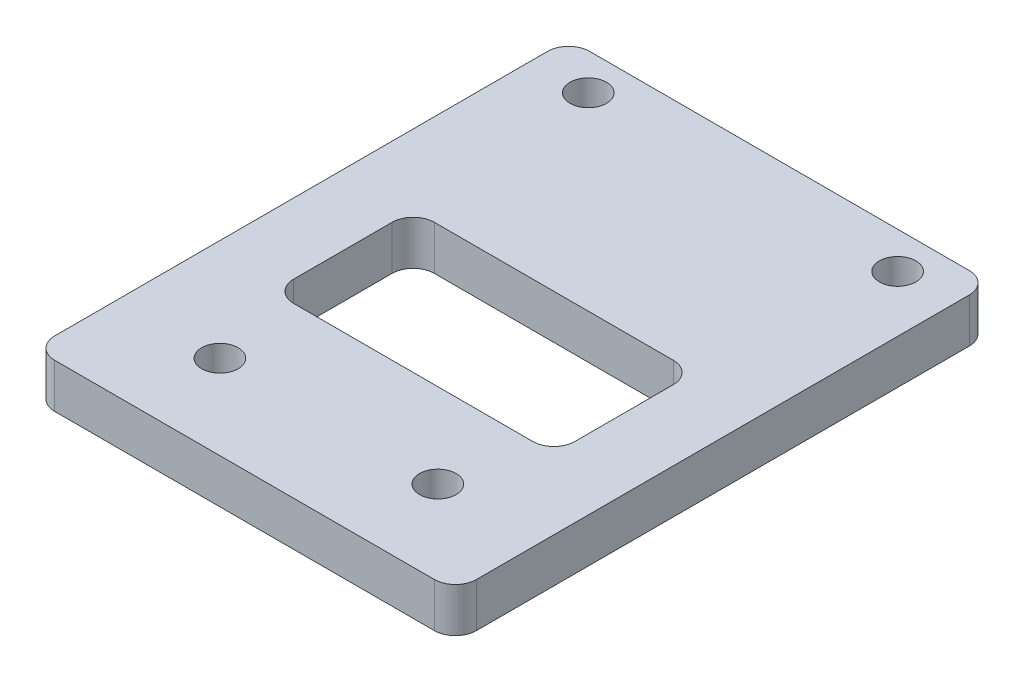
SolidWorks part; units mm, degrees
ref_plane "Front Plane" through (0, 0, 0) normal (0, 0, 1) x (1, 0, 0)
ref_plane "Top Plane" through (0, 0, 0) normal (0, 1, 0) x (1, 0, 0)
ref_plane "Right Plane" through (0, 0, 0) normal (1, 0, 0) x (0, 0, -1)
sketch "Sketch1" plane through (0, 0, 0) normal (0, 1, 0) x (1, 0, 0)
  line L1 (-15, 19.025) -> (15, 19.025)
  line L2 (-15, 19.025) -> (-15, -19.025)
  line L3 (-15, -19.025) -> (15, -19.025)
  line L4 (15, 19.025) -> (15, -19.025)
  dimension "D1" = 30
  dimension "D2" = 38.05
  dimension "D3" = 19.025
  dimension "D4" = 15
extrude "Boss-Extrude1" add sketch "Sketch1" against normal blind 3.15
sketch "Sketch2" plane through (0, 0, 0) normal (0, 1, 0) x (1, 0, 0)
  line L0 (15, 19.025) -> (-15, 19.025) construction
  line L1 (-8.5, 2.975) -> (8.5, 2.975)
  line L2 (-10, 1.475) -> (-10, -5.525)
  line L3 (-8.5, -7.025) -> (8.5, -7.025)
  line L4 (10, 1.475) -> (10, -5.525)
  line L5 (-15, 19.025) -> (-15, -19.025) construction
  line L6 (15, -19.025) -> (15, 19.025) construction
  arc A0 (-10, -5.525) -> (-8.5, -7.025) centre (-8.5, -5.525) ccw
  arc A1 (8.5, -7.025) -> (10, -5.525) centre (8.5, -5.525) ccw
  arc A2 (8.5, 2.975) -> (10, 1.475) centre (8.5, 1.475) cw
  arc A3 (-8.5, 2.975) -> (-10, 1.475) centre (-8.5, 1.475) ccw
  point P10 (0, 0)
  point P15 (10, -7.025)
  point P18 (10, 2.975)
  dimension "D5" = 1.5
  dimension "D1" = 16.05
  dimension "D2" = 10
  dimension "D3" = 5
  dimension "D4" = 5
extrude "Cut-Extrude1" cut sketch "Sketch2" against normal through all
sketch "Sketch3" plane through (0, 0, 0) normal (0, 1, 0) x (1, 0, 0)
  line L0 (15, 19.025) -> (-15, 19.025) construction
  line L1 (-15, 19.025) -> (-15, -19.025) construction
  circle A0 centre (-11, 16.425) radius 1.3
  circle A1 centre (11, 16.425) radius 1.3
  dimension "D1" = 2.6
  dimension "D2" = 2.6
  dimension "D3" = 2.6
  dimension "D4" = 2.6
  dimension "D5" = 22
  dimension "D6" = 4
extrude "Cut-Extrude2" cut sketch "Sketch3" against normal through all
fillet "Fillet1" radius 1.5 4 edges at (15, -1.575, -19.025) (-15, -1.575, -19.025) (15, -1.575, 19.025) (-15, -1.575, 19.025)
sketch "Sketch5" plane through (0, 0, 0) normal (0, 1, 0) x (1, 0, 0)
  line L0 (-8.5, -7.025) -> (8.5, -7.025) construction
  line L1 (-15, 17.525) -> (-15, -17.525) construction
  circle A0 centre (-7.75, -13.025) radius 1.3
  circle A1 centre (7.75, -13.025) radius 1.3
  dimension "D1" = 2.6
  dimension "D2" = 2.6
  dimension "D3" = 15.5
  dimension "D4" = 6
  dimension "D5" = 6
  dimension "D6" = 7.25
extrude "Cut-Extrude3" cut sketch "Sketch5" against normal through all
equation "\"PLATE_WIDTH\"=30"
equation "\"D1@Sketch1\"=\"PLATE_WIDTH\""
equation "\"PLATE_HEIGHT\"=38.05"
equation "\"D2@Sketch1\"=\"PLATE_HEIGHT\""
equation "\"D3@Sketch1\"=\"D2@Sketch1\"/2"
equation "\"D4@Sketch1\"=\"D1@Sketch1\"/2"
equation "\"D6@Sketch5\"=(\"PLATE_WIDTH\"-\"D3@Sketch5\")/2"
